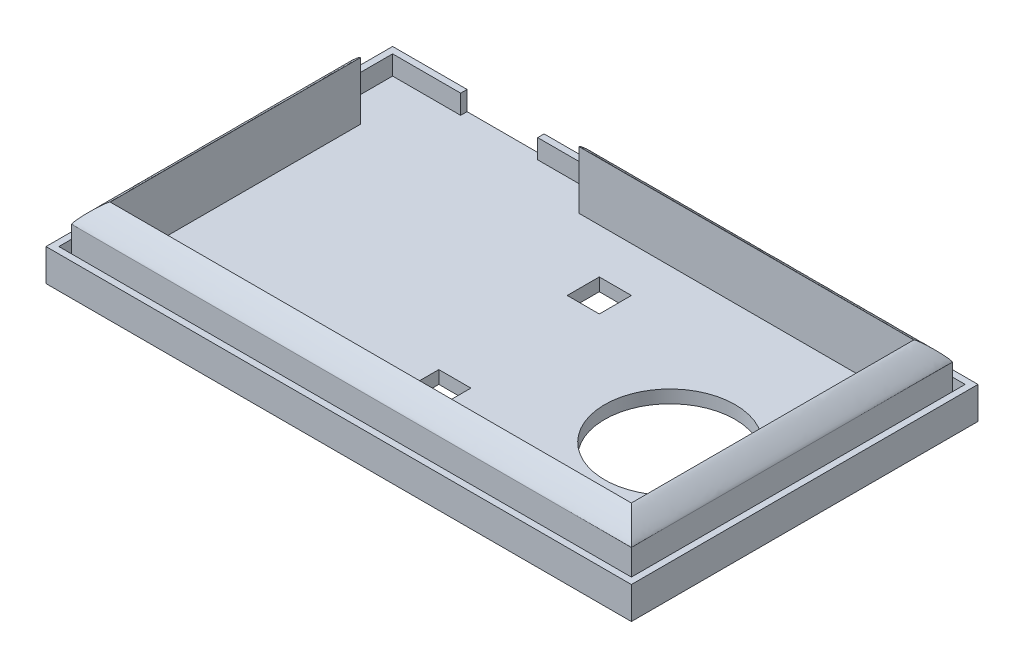
SolidWorks part; units mm, degrees
ref_plane "Alzado" through (0, 0, 0) normal (0, 0, 1) x (1, 0, 0)
ref_plane "Planta" through (0, 0, 0) normal (0, 1, 0) x (1, 0, 0)
ref_plane "Vista lateral" through (0, 0, 0) normal (1, 0, 0) x (0, 0, -1)
sketch "Croquis1" plane through (0, 0, 0) normal (0, 1, 0) x (1, 0, 0)
  line L1 (-45.6, -27) -> (45.6, -27)
  line L2 (-45.6, -27) -> (-45.6, 27)
  line L3 (-45.6, 27) -> (45.6, 27)
  line L4 (45.6, -27) -> (45.6, 27)
  line L5 (-45.6, -27) -> (45.6, 27) construction
  line L6 (-45.6, 27) -> (45.6, -27) construction
  point P0 (0, 0)
  dimension "D1" = 54
  dimension "D2" = 91.2
extrude "Saliente-Extruir1" add sketch "Croquis1" along normal blind 2
sketch "Croquis2" plane through (0, 2, 0) normal (0, 1, 0) x (1, 0, 0)
  line L1 (-44.6, -26) -> (44.6, -26)
  line L2 (-44.6, -26) -> (-44.6, 26)
  line L3 (-44.6, 26) -> (44.6, 26)
  line L4 (44.6, -26) -> (44.6, 26)
  line L5 (-44.6, -26) -> (44.6, 26) construction
  line L6 (-44.6, 26) -> (44.6, -26) construction
  line L7 (45.6, -27) -> (-45.6, -27)
  line L8 (45.6, -27) -> (45.6, 27)
  line L9 (45.6, 27) -> (-45.6, 27)
  line L10 (-45.6, -27) -> (-45.6, 27)
  line L11 (45.6, -27) -> (-45.6, 27) construction
  line L12 (45.6, 27) -> (-45.6, -27) construction
  point P0 (0, 0)
  point P6 (0, 0)
  dimension "D1" = 1
  dimension "D2" = 1
extrude "Saliente-Extruir2" add sketch "Croquis2" along normal blind 3
sketch "Croquis3" plane through (0, 2, 0) normal (0, 1, 0) x (1, 0, 0)
  line L0 (45.6, -27) -> (45.6, 27) construction
  line L1 (-43.6, -25) -> (43.6, -25)
  line L2 (-43.6, -25) -> (-43.6, 25)
  line L3 (-43.6, 25) -> (43.6, 25)
  line L4 (43.6, -25) -> (43.6, 25)
  line L5 (-43.6, -25) -> (43.6, 25) construction
  line L6 (-43.6, 25) -> (43.6, -25) construction
  line L7 (-40.6, -22) -> (40.6, -22)
  line L8 (-40.6, -22) -> (-40.6, 22)
  line L9 (-40.6, 22) -> (40.6, 22)
  line L10 (40.6, -22) -> (40.6, 22)
  line L11 (-40.6, -22) -> (40.6, 22) construction
  line L12 (-40.6, 22) -> (40.6, -22) construction
  line L13 (45.6, 27) -> (-45.6, 27) construction
  line L14 (-45.6, 27) -> (-45.6, -27) construction
  line L15 (-39.6, 21) -> (33.6, 21) construction
  line L16 (-39.6, 21) -> (-39.6, -21) construction
  line L17 (-39.6, -21) -> (33.6, -21) construction
  line L18 (33.6, 21) -> (33.6, -21) construction
  line L19 (-45.6, -27) -> (45.6, -27) construction
  point P0 (0, 0)
  point P6 (0, 0)
  dimension "D1" = 2
  dimension "D2" = 2
  dimension "D3" = 3
  dimension "D4" = 3
  dimension "D5" = 6
  dimension "D6" = 6
  dimension "D7" = 6
  dimension "D8" = 12
extrude "Saliente-Extruir3" add sketch "Croquis3" along normal blind 9
fillet "Redondeo1" radius 3 4 edges at (0, 11, -25) (43.6, 11, 0) (-43.6, 11, 0) (0, 11, 25) conic rho 0.1
sketch "Croquis4" plane through (0, 2, 0) normal (0, 1, 0) x (1, 0, 0)
  line L1 (-43.6, 17) -> (-11.6, 17)
  line L2 (-43.6, 17) -> (-43.6, 25)
  line L3 (-43.6, 25) -> (-11.6, 25)
  line L4 (-11.6, 17) -> (-11.6, 25)
  dimension "D1" = 8
  dimension "D2" = 32
extrude "Cortar-Extruir2" cut sketch "Croquis4" along normal blind 28
sketch "Croquis5" plane through (0, 0, 0) normal (0, -1, 0) x (1, 0, 0)
  line L0 (-45.6, 27) -> (45.6, 27) construction
  line L1 (-39.6, -21) -> (33.6, -21) construction
  line L2 (-39.6, -21) -> (-39.6, 21) construction
  line L3 (-39.6, 21) -> (33.6, 21) construction
  line L4 (33.6, -21) -> (33.6, 21) construction
  line L5 (45.6, -27) -> (-45.6, -27) construction
  line L6 (-45.6, -27) -> (-45.6, 27) construction
  line L7 (45.6, 27) -> (45.6, -27) construction
  line L8 (-45.6, 0) -> (45.6, 0) construction
  line L9 (-1.4, 10) -> (3.6, 10)
  line L10 (-1.4, 10) -> (-1.4, 15)
  line L11 (-1.4, 15) -> (3.6, 15)
  line L12 (3.6, 10) -> (3.6, 15)
  line L13 (-1.4, 10) -> (3.6, 15) construction
  line L14 (-1.4, 15) -> (3.6, 10) construction
  line L15 (-1.4, -15) -> (3.6, -10) construction
  line L16 (-1.4, -10) -> (3.6, -15) construction
  line L17 (3.6, -10) -> (3.6, -15)
  line L18 (-1.4, -15) -> (3.6, -15)
  line L19 (-1.4, -10) -> (-1.4, -15)
  line L20 (-1.4, -10) -> (3.6, -10)
  circle A0 centre (26.4, 1.8) radius 10.16
  point P14 (1.1, 12.5)
  point P25 (1.1, -12.5)
  dimension "D5" = 66
  dimension "D6" = 22.8
  dimension "D7" = 20.32
  dimension "D1" = 6
  dimension "D2" = 6
  dimension "D3" = 6
  dimension "D4" = 12
  dimension "D8" = 5
  dimension "D9" = 5
  dimension "D10" = 12
  dimension "D11" = 42
extrude "Cortar-Extruir3" cut sketch "Croquis5" against normal blind 28
sketch "Croquis6" plane through (0, 0, -27) normal (0, 0, -1) x (-1, 0, 0)
  line L0 (-45.6, 5) -> (45.6, 5) construction
  line L1 (34, 8) -> (22, 8)
  line L2 (34, 8) -> (34, 2)
  line L3 (34, 2) -> (22, 2)
  line L4 (22, 8) -> (22, 2)
  line L5 (34, 8) -> (22, 2) construction
  line L6 (34, 2) -> (22, 8) construction
  line L7 (45.6, 5) -> (45.6, 0) construction
  line L8 (29.7, 0) -> (-29.7, 0) construction
  point P0 (28, 5)
  dimension "D1" = 17.6
  dimension "D2" = 2
  dimension "D3" = 12
extrude "Cortar-Extruir4" cut sketch "Croquis6" against normal blind 7
